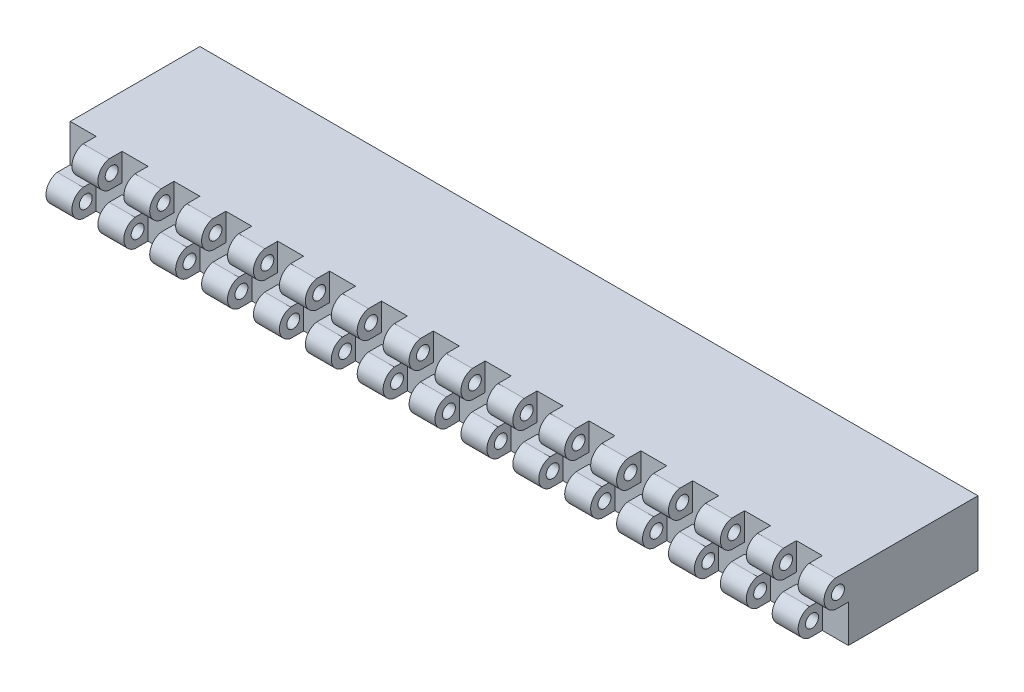
SolidWorks part; units mm, degrees
ref_plane "Front Plane" through (0, 0, 0) normal (0, 0, 1) x (1, 0, 0)
ref_plane "Top Plane" through (0, 0, 0) normal (0, 1, 0) x (1, 0, 0)
ref_plane "Right Plane" through (0, 0, 0) normal (1, 0, 0) x (0, 0, -1)
sketch "Sketch1" plane through (0, 0, 0) normal (1, 0, 0) x (0, 0, -1)
  line L1 (-25, 12.5) -> (25, 12.5)
  line L2 (-25, 12.5) -> (-25, -12.5)
  line L3 (-25, -12.5) -> (25, -12.5)
  line L4 (25, 12.5) -> (25, -12.5)
  line L5 (-25, 12.5) -> (25, -12.5) construction
  line L6 (-25, -12.5) -> (25, 12.5) construction
  point P0 (0, 0)
  dimension "D1" = 25
  dimension "D2" = 50
extrude "Boss-Extrude1" add sketch "Sketch1" along normal mid plane 300
sketch "Sketch2" plane through (150, 0, 0) normal (1, 0, 0) x (0, 0, -1)
  line L1 (-25, -12.5) -> (-25, 2) construction
  line L2 (-25, 2) -> (-25, 12.5)
  line L3 (-25, 2) -> (-30, 2)
  line L4 (-25, 12.5) -> (-30, 12.5)
  line L5 (25, 12.5) -> (-25, 12.5) construction
  arc A1 (-30, 12.5) -> (-30, 2) centre (-29, 7.25) ccw
  circle A2 centre (-29, 7.25) radius 2.5
  point P7 (-25, 7.25)
  dimension "D3" = 5
  dimension "D1" = 10.5
  dimension "D2" = 5
  dimension "D4" = 4
extrude "Boss-Extrude2" add sketch "Sketch2" against normal blind 10
pattern_linear "LPattern1" count 15 spacing 20 along (-1, 0, 0) of "Boss-Extrude2"
sketch "Sketch4" plane through (0, 0, -25) normal (0, 0, -1) x (-1, 0, 0)
  circle A0 centre (0, 0) radius 8
  dimension "D1" = 16
extrude "Cut-Extrude1" cut sketch "Sketch4" against normal blind 30
sketch "Sketch3" plane through (-150, 0, 0) normal (-1, 0, 0) x (0, 0, 1)
  line L0 (25, -12.5) -> (25, 0)
  line L1 (25, 12.5) -> (25, -12.5) construction
  line L2 (25, -12.5) -> (-25, -12.5) construction
  line L3 (25, -2) -> (30, -2)
  line L4 (25, -12.5) -> (30, -12.5)
  arc A1 (30, -12.5) -> (30, -2) centre (29, -7.25) ccw
  circle A2 centre (29, -7.25) radius 2.5
  point P7 (25, -6.25)
  dimension "D2" = 4
  dimension "D3" = 5
  dimension "D1" = 5
  dimension "D4" = 10.5
extrude "Boss-Extrude3" add sketch "Sketch3" against normal blind 10 contours L4 A1 L3 L0 A2 region at (-150, -7.25, 25.1406)
pattern_linear "LPattern2" count 15 spacing 20 along (1, 0, 0) of "Boss-Extrude3"
